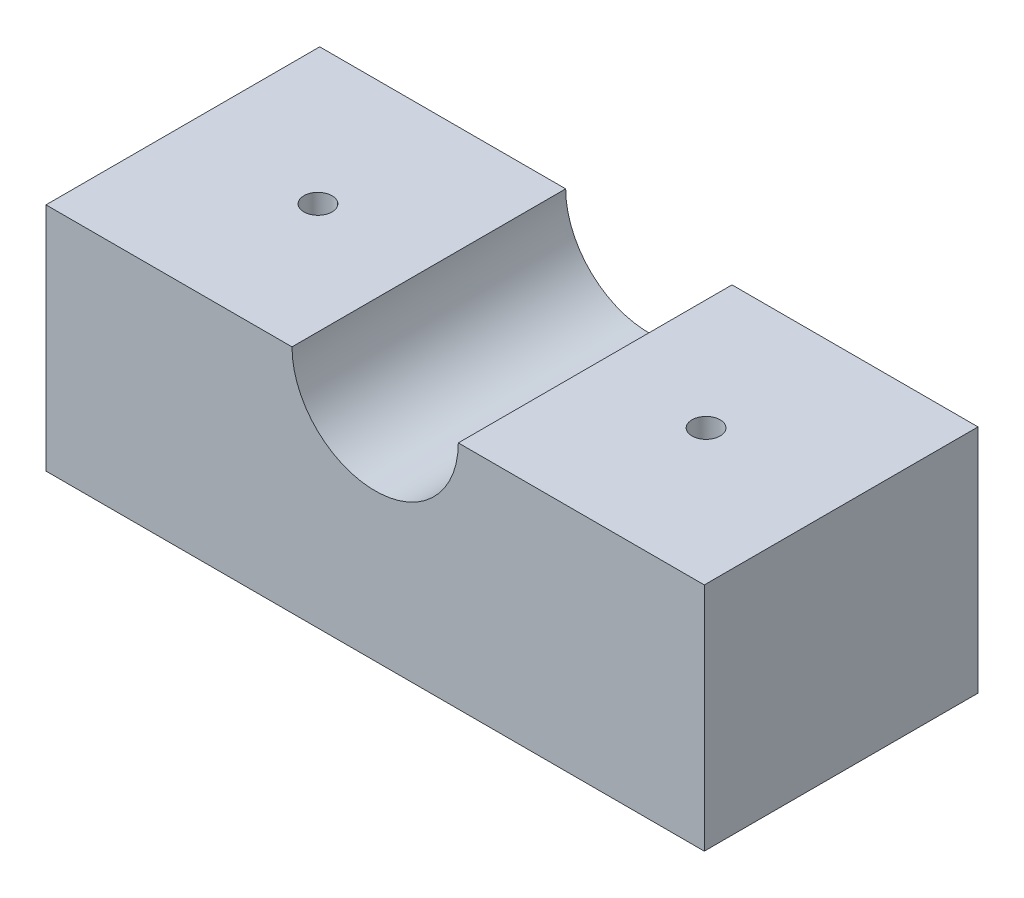
SolidWorks part; units mm, degrees
material "Custom Plastic"
ref_plane "Front Plane" through (0, 0, 0) normal (0, 0, 1) x (1, 0, 0)
ref_plane "Top Plane" through (0, 0, 0) normal (0, 1, 0) x (1, 0, 0)
ref_plane "Right Plane" through (0, 0, 0) normal (1, 0, 0) x (0, 0, -1)
sketch "Sketch2" plane through (0, 0, 0) normal (0, 1, 0) x (1, 0, 0)
  line L0 (-11.873, 4.9365) -> (11.873, 4.9365)
  line L1 (11.873, 4.9365) -> (11.873, -4.9365)
  line L2 (11.873, -4.9365) -> (-11.873, -4.9365)
  line L3 (-11.873, -4.9365) -> (-11.873, 4.9365)
  dimension "D1" = 11.873
  dimension "D2" = 4.9365
  dimension "D3" = 4.9365
  dimension "D4" = 11.873
extrude "Boss-Extrude1" add sketch "Sketch2" along normal blind 8.3185 contours L0 L1 L2 L3
sketch "Sketch3" plane through (0, 0, 4.9365) normal (0, 0, 1) x (1, 0, 0)
  line L0 (11.873, 8.3185) -> (-11.873, 8.3185) construction
  circle A0 centre (0, 8.3185) radius 2.9997
extrude "Cut-Extrude1" cut sketch "Sketch3" against normal through all contours A0
sketch "Sketch4" plane through (0, 8.3185, 0) normal (0, 1, 0) x (1, 0, 0)
  circle A0 centre (-7, 0) radius 0.508
  circle A1 centre (7, 0) radius 0.508
  point P7 (0, 0)
extrude "Cut-Extrude2" cut sketch "Sketch4" against normal blind 2.54
